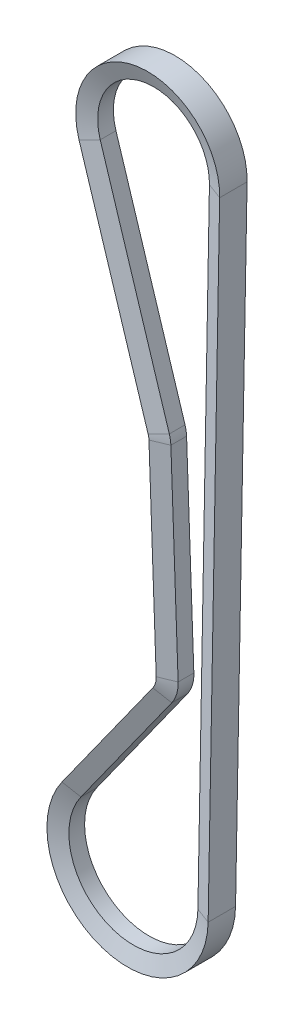
SolidWorks part; units mm, degrees
ref_plane "Front Plane" through (0, 0, 0) normal (0, 0, 1) x (1, 0, 0)
ref_plane "Top Plane" through (0, 0, 0) normal (0, 1, 0) x (1, 0, 0)
ref_plane "Right Plane" through (0, 0, 0) normal (1, 0, 0) x (0, 0, -1)
sketch "Sketch2" plane through (0, 0, 0) normal (0, 0, 1) x (1, 0, 0)
  line L0 (0, 0) -> (1, 0) construction
  line L1 (0, 0) -> (0, 1) construction
  line L12 (24.9959, -0.4548) -> (20.9938, -220.398)
  line L14 (-29.7732, -203.5958) -> (1.7732, -159.505)
  line L15 (2.9548, -155.5813) -> (0.4339, -85.6267)
  line L16 (0.1467, -83.9539) -> (-23.8528, -7.4862)
  arc A4 (20.9938, -220.398) -> (-29.7732, -203.5958) centre (-7.0016, -219.8886) cw
  arc A7 (-23.8528, -7.4862) -> (24.9959, -0.4548) centre (0, 0) cw
  arc A8 (1.7732, -159.505) -> (2.9548, -155.5813) centre (-3.3911, -155.81) ccw
  arc A9 (0.4339, -85.6267) -> (0.1467, -83.9539) centre (-5.912, -85.8554) ccw
ref_plane "Plane4" through (-23.8528, -7.4862, 0) normal (-0.2994, 0.9541, 0) x (0.9541, 0.2994, 0)
sketch "Sketch3" plane through (-23.8528, -7.4862, 0) normal (-0.2994, 0.9541, 0) x (0.9541, 0.2994, 0)
  line L0 (0, -4.7625) -> (0, 4.7625)
  line L1 (0, -4.7625) -> (5.588, -2.7286)
  line L2 (5.588, -2.7286) -> (5.588, 2.7286)
  line L3 (5.588, 2.7286) -> (0, 4.7625)
  line L4 (0, 0) -> (5.588, 0) construction
  dimension "D1" = 9.525
  dimension "D2" = 5.588
  dimension "D3" = 40
sweep "Sweep1" add profiles "Sketch3" path "Sketch2"
